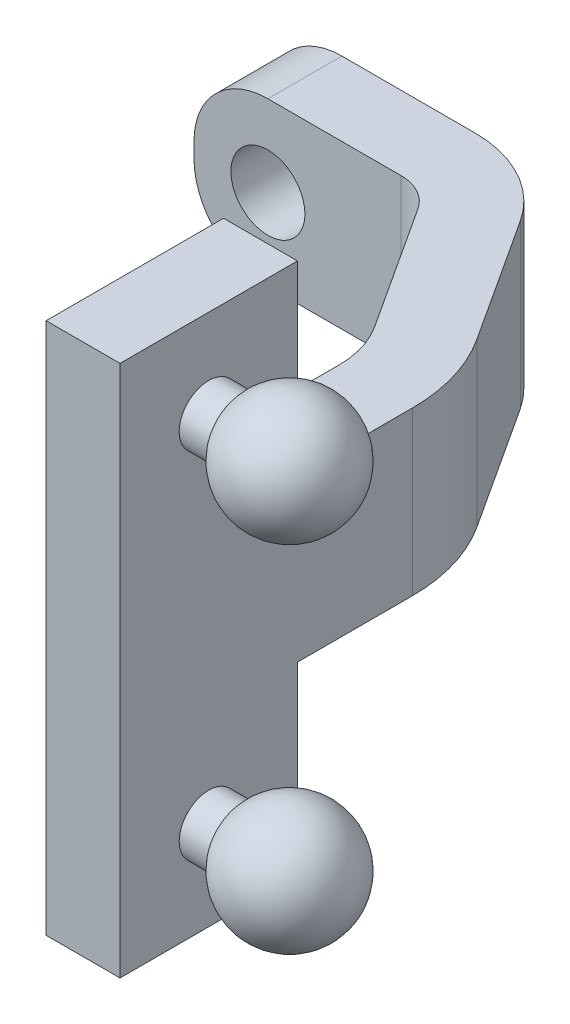
SolidWorks part; units mm, degrees
ref_plane "前视基准面" through (0, 0, 0) normal (0, 0, 1) x (1, 0, 0)
ref_plane "上视基准面" through (0, 0, 0) normal (0, 1, 0) x (1, 0, 0)
ref_plane "右视基准面" through (0, 0, 0) normal (1, 0, 0) x (0, 0, -1)
other "Configuration Table"
sketch "草图1" plane through (0, 0, 0) normal (0, 1, 0) x (1, 0, 0)
  line L0 (0, 0) -> (7, 0)
  line L1 (14, -9.1042) -> (14, -19)
  line L2 (0, -2.5) -> (7, -2.5)
  line L3 (11.5, -9.1042) -> (11.5, -19)
  line L4 (11.5, -19) -> (14, -19)
  line L5 (0, 0) -> (0, -2.5)
  line L6 (10.3535, -1.8196) -> (13.0862, -6.0224)
  line L7 (8.2575, -3.1823) -> (10.9903, -7.3852)
  arc A0 (7, 0) -> (10.3535, -1.8196) centre (7, -4) cw
  arc A3 (7, -2.5) -> (8.2575, -3.1823) centre (7, -4) cw
  arc A6 (9.6623, -0.4928) -> (14, -9.1042) centre (3.2834, -9.1042) cw construction
  arc A7 (10.3535, -1.8196) -> (9.6623, -0.4928) centre (16.8788, 2.4233) ccw construction
  arc A8 (8.2575, -3.1823) -> (7.6722, -2.1578) centre (16.8788, 2.4233) ccw construction
  arc A9 (7.6722, -2.1578) -> (11.5, -9.1042) centre (3.2834, -9.1042) cw construction
  arc A10 (13.0862, -6.0224) -> (14, -9.1042) centre (8.3466, -9.1042) cw
  arc A11 (11.5, -9.1042) -> (10.9903, -7.3852) centre (8.3466, -9.1042) ccw
  dimension "D1" = 2.5
  dimension "D3" = 4
  dimension "D4" = 14
  dimension "D2" = 7
  dimension "D6" = 19
extrude "凸台-拉伸1" add sketch "草图1" along normal mid plane 5.5
sketch "草图2" plane through (0, 0, 0) normal (0, 0, -1) x (-1, 0, 0)
  line L0 (0, 2.75) -> (0, -2.75) construction
  circle A0 centre (-2.5, 0) radius 1.25
  point P5 (0, 0)
  dimension "D1" = 2.5
  dimension "D2" = 2.5
extrude "切除-拉伸1" cut sketch "草图2" against normal blind 10
fillet "圆角2" radius 2.5 2 edges at (0, -2.75, 1.25) (0, 2.75, 1.25)
sketch "草图4" plane through (11.5, 0, 0) normal (-1, 0, 0) x (0, 0, 1)
  line L0 (19, 2.75) -> (19, -2.75) construction
  line L1 (13, 9) -> (19, 9)
  line L2 (13, 9) -> (13, -9)
  line L3 (13, -9) -> (19, -9)
  line L4 (19, 9) -> (19, -9)
  line L5 (13, 9) -> (19, -9) construction
  line L6 (13, -9) -> (19, 9) construction
  point P0 (16, 0)
  dimension "D1" = 18
  dimension "D2" = 6
extrude "凸台-拉伸2" add sketch "草图4" against normal up to surface (2.5 mm away) up to face at (14, 0, 14.0521)
sketch "草图5" plane through (14, 0, 0) normal (1, 0, 0) x (0, 0, -1)
  line L0 (-13, 9) -> (-19, 9) construction
  line L1 (-13, 2.75) -> (-13, 9) construction
  circle A0 centre (-16, 6) radius 1
  dimension "D1" = 2
  dimension "D2" = 3
  dimension "D3" = 3
extrude "凸台-拉伸3" add sketch "草图5" along normal blind 1
ref_axis "基准轴1" through (15, 6, 16) along (-1, 0, 0)
ref_plane "基准面1" through (0, 0, 16) normal (0, 0, -1) x (-1, 0, 0)
sketch "草图6" plane through (0, 0, 16) normal (0, 0, -1) x (-1, 0, 0)
  line L0 (-15, 6) -> (-18.7321, 6)
  line L1 (-15, 7) -> (-15, 5) construction
  line L2 (-15, 6) -> (-14, 6) construction
  line L3 (-15, 6) -> (-15, 7)
  line L4 (-14, 7) -> (-15, 7) construction
  arc A0 (-15, 7) -> (-18.7321, 6) centre (-16.7321, 6) ccw
  dimension "D1" = 4
revolve "旋转1" add sketch "草图6" angle 360 about L0
mirror "镜向1" about plane through (0, 0, 0) normal (0, 1, 0) of "凸台-拉伸3", "旋转1"
